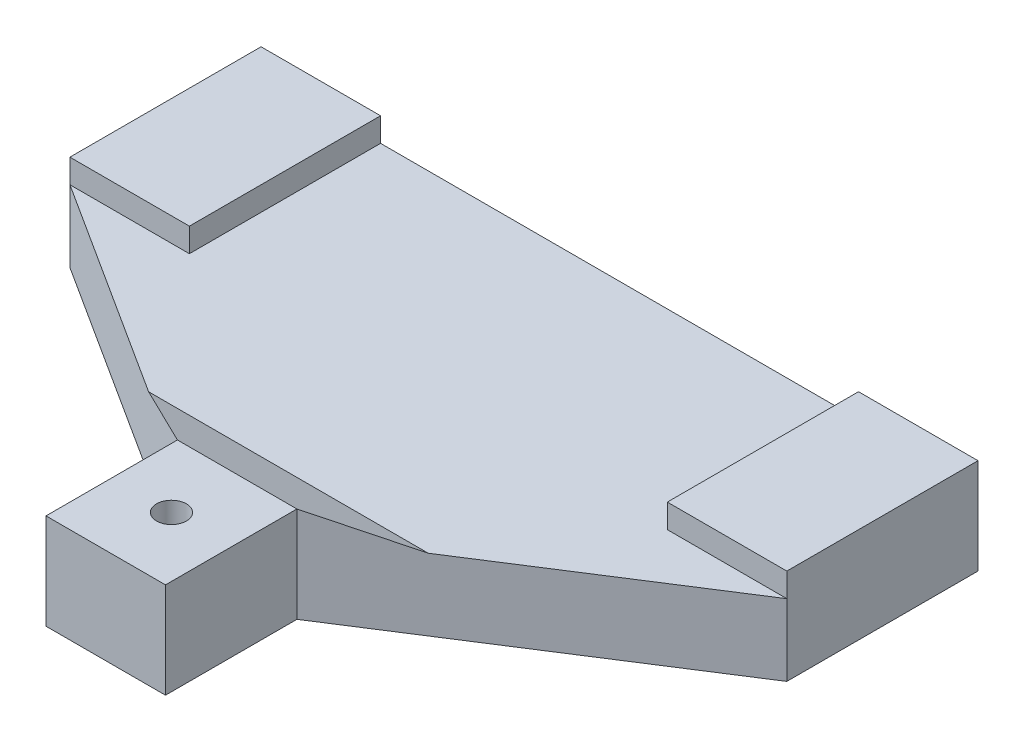
SolidWorks part; units mm, degrees
ref_plane "Plan de face" through (0, 0, 0) normal (0, 0, 1) x (1, 0, 0)
ref_plane "Plan de dessus" through (0, 0, 0) normal (0, 1, 0) x (1, 0, 0)
ref_plane "Plan de droite" through (0, 0, 0) normal (1, 0, 0) x (0, 0, -1)
sketch "Esquisse1" plane through (0, 0, 0) normal (0, 0, 1) x (1, 0, 0)
  line L1 (0, 0) -> (60, 0)
  line L2 (0, 0) -> (0, 8)
  line L3 (0, 8) -> (60, 8)
  line L4 (60, 0) -> (60, 8)
  dimension "D1" = 8
  dimension "D2" = 60
extrude "Boss.-Extru.1" add sketch "Esquisse1" along normal blind 60
sketch "Esquisse2" plane through (0, 0, 0) normal (0, 0, -1) x (-1, 0, 0)
  line L0 (-60, 8) -> (0, 8) construction
  line L1 (-60, 0) -> (-60, 8) construction
  line L2 (0, 8) -> (0, 0) construction
  circle A0 centre (-54, 4) radius 1.25
  circle A1 centre (-5.75, 4) radius 1.25
  dimension "D6" = 2.5
  dimension "D7" = 2.5
  dimension "D1" = 48.25
  dimension "D2" = 4
  dimension "D3" = 4
  dimension "D4" = 6
  dimension "D5" = 5.75
extrude "Enlèv. mat.-Extru.1" cut sketch "Esquisse2" against normal blind 15
sketch "Esquisse3" plane through (0, 8, 0) normal (0, 1, 0) x (1, 0, 0)
  line L0 (60, -60) -> (60, 0) construction
  line L1 (60, 0) -> (0, 0) construction
  circle A0 centre (30, -37.5) radius 1.25
  dimension "D1" = 2.5
  dimension "D2" = 30
  dimension "D3" = 37.5
extrude "Enlèv. mat.-Extru.2" cut sketch "Esquisse3" against normal blind 15
sketch "Esquisse4" plane through (0, 8, 0) normal (0, 1, 0) x (1, 0, 0)
  line L0 (0, -16) -> (10, -16)
  line L1 (0, -60) -> (0, 0) construction
  line L2 (10, -16) -> (10, 0)
  line L3 (60, 0) -> (0, 0) construction
  line L4 (10, 0) -> (50, 0)
  line L5 (50, 0) -> (50, -16)
  line L6 (50, -16) -> (60, -16)
  line L7 (60, -60) -> (60, 0) construction
  line L8 (60, -16) -> (60, -60)
  line L9 (60, -60) -> (0, -60)
  line L10 (0, -60) -> (0, -16)
  line L11 (25, -43) -> (35, -43)
  line L12 (35, -43) -> (35, -32)
  line L13 (35, -32) -> (25, -32)
  line L14 (25, -32) -> (25, -43)
  dimension "D1" = 10
  dimension "D2" = 10
  dimension "D3" = 16
  dimension "D4" = 16
  dimension "D5" = 17
  dimension "D6" = 32
  dimension "D7" = 25
  dimension "D8" = 25
extrude "Enlèv. mat.-Extru.3" cut sketch "Esquisse4" against normal blind 2
sketch "Esquisse5" plane through (0, 6, 0) normal (0, 1, 0) x (1, 0, 0)
  line L0 (60, -16) -> (35, -32)
  line L1 (35, -32) -> (35, -43)
  line L2 (35, -43) -> (25, -43)
  line L3 (25, -43) -> (25, -32)
  line L4 (25, -32) -> (0, -16)
  line L5 (0, -16) -> (-21.5949, -85.4755)
  line L6 (-21.5949, -85.4755) -> (75.4145, -69.9308)
  line L7 (75.4145, -69.9308) -> (60, -16)
extrude "Enlèv. mat.-Extru.4" cut sketch "Esquisse5" against normal blind 52
chamfer "Chanfrein1" distance 2 angle 65 1 edges at (30, 6, 32) first distance on face at (30, 7, 32)
